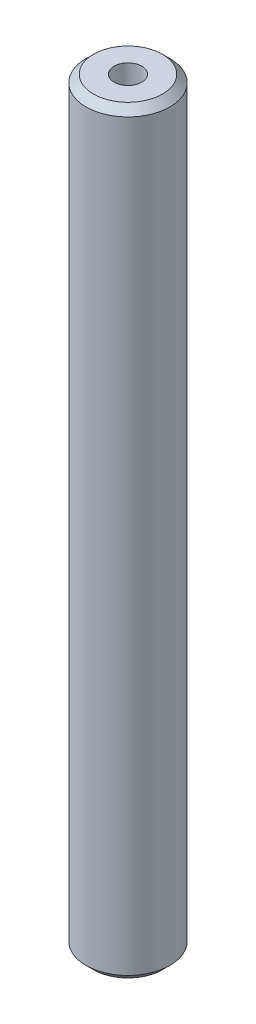
SolidWorks part; units mm, degrees
ref_plane "Front Plane" through (0, 0, 0) normal (0, 0, 1) x (1, 0, 0)
ref_plane "Top Plane" through (0, 0, 0) normal (0, 1, 0) x (1, 0, 0)
ref_plane "Right Plane" through (0, 0, 0) normal (1, 0, 0) x (0, 0, -1)
sketch "Sketch1" plane through (0, 0, 0) normal (0, 1, 0) x (1, 0, 0)
  circle A0 centre (0, 0) radius 22.5
  dimension "SHAFT_OD" = 45
extrude "Boss-Extrude1" add sketch "Sketch1" along normal blind 407.0719
sketch "Sketch2" plane through (0, 0, 0) normal (0, 1, 0) x (1, 0, 0)
  circle A0 centre (0, 0) radius 7.4468
  dimension "BORE_D" = 14.8936
extrude "Cut-Extrude1" cut sketch "Sketch2" along normal through all
chamfer "Chamfer1" distance 3.9864 angle 45 2 edges at (0, 407.0719, 22.5) (0, 0, 22.5)
